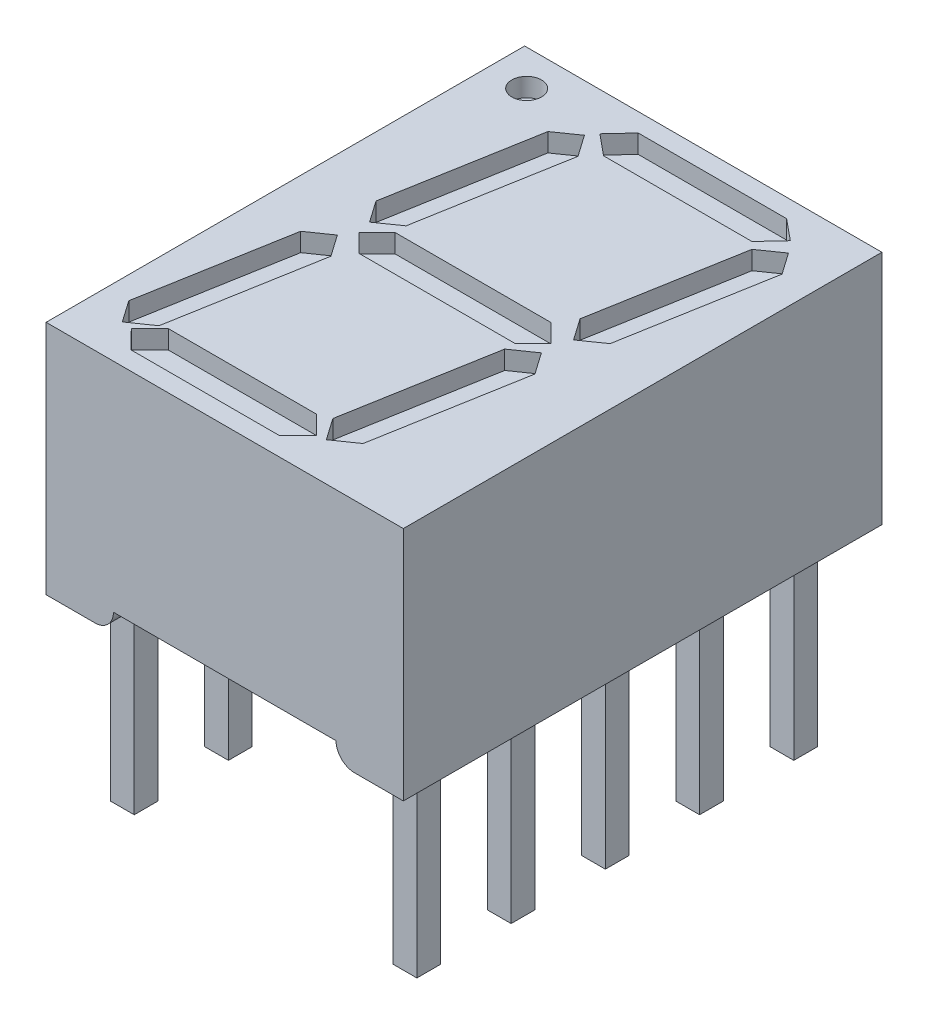
SolidWorks part; units mm, degrees
ref_plane "Front Plane" through (0, 0, 0) normal (0, 0, 1) x (1, 0, 0)
ref_plane "Top Plane" through (0, 0, 0) normal (0, 1, 0) x (1, 0, 0)
ref_plane "Right Plane" through (0, 0, 0) normal (1, 0, 0) x (0, 0, -1)
sketch "Sketch1" plane through (0, 0, 0) normal (0, 1, 0) x (1, 0, 0)
  line L1 (-4.815, -6.45) -> (4.815, -6.45)
  line L2 (-4.815, -6.45) -> (-4.815, 6.45)
  line L3 (-4.815, 6.45) -> (4.815, 6.45)
  line L4 (4.815, -6.45) -> (4.815, 6.45)
  line L5 (-4.815, -6.45) -> (4.815, 6.45) construction
  line L6 (-4.815, 6.45) -> (4.815, -6.45) construction
  point P0 (0, 0)
  dimension "D1" = 12.9
  dimension "D2" = 9.63
extrude "Boss-Extrude1" add sketch "Sketch1" along normal blind 6.36
sketch "Sketch2" plane through (0, 0, 0) normal (0, -1, 0) x (1, 0, 0)
  line L0 (-4.815, 6.45) -> (4.815, 6.45) construction
  line L1 (3, -6.45) -> (-3, -6.45)
  line L2 (3, -6.45) -> (3, 6.45)
  line L3 (3, 6.45) -> (-3, 6.45)
  line L4 (-3, -6.45) -> (-3, 6.45)
  line L5 (3, -6.45) -> (-3, 6.45) construction
  line L6 (3, 6.45) -> (-3, -6.45) construction
  line L7 (4.815, -6.45) -> (-4.815, -6.45) construction
  point P0 (0, 0)
  dimension "D1" = 6
extrude "Cut-Extrude1" cut sketch "Sketch2" against normal blind 0.5
fillet "Fillet1" radius 0.5 2 edges at (3, 0, 0) (-3, 0, 0)
sketch "Sketch3" plane through (0, 0, 0) normal (0, -1, 0) x (1, 0, 0)
  line L0 (-3.49, 2.86) -> (-4.13, 2.22) construction
  line L1 (3.81, -6.45) -> (-3.81, -6.45) construction
  line L2 (3.81, -6.45) -> (3.81, 6.45) construction
  line L3 (3.81, 6.45) -> (-3.81, 6.45) construction
  line L4 (-3.81, -6.45) -> (-3.81, 6.45) construction
  line L5 (3.81, -6.45) -> (-3.81, 6.45) construction
  line L6 (3.81, 6.45) -> (-3.81, -6.45) construction
  line L7 (3.5, 6.45) -> (4.815, 6.45) construction
  line L8 (4.815, -6.45) -> (3.5, -6.45) construction
  line L9 (-4.815, 0) -> (4.815, 0) construction
  line L10 (-4.815, -6.45) -> (-4.815, 6.45) construction
  line L11 (4.815, 6.45) -> (4.815, -6.45) construction
  line L12 (-4.815, 2.54) -> (4.815, 2.54) construction
  line L13 (-4.815, 5.08) -> (4.815, 5.08) construction
  line L14 (-4.815, -2.54) -> (4.815, -2.54) construction
  line L15 (-4.815, -5.08) -> (4.815, -5.08) construction
  line L16 (-3.49, 2.22) -> (-3.49, 2.86)
  line L17 (-3.49, 4.76) -> (-4.13, 4.76)
  line L18 (-3.49, 4.76) -> (-3.49, 5.4)
  line L19 (-3.49, 5.4) -> (-4.13, 5.4)
  line L20 (-4.13, 4.76) -> (-4.13, 5.4)
  line L21 (-3.49, 4.76) -> (-4.13, 5.4) construction
  line L22 (-3.49, 5.4) -> (-4.13, 4.76) construction
  line L23 (-3.49, 2.22) -> (-4.13, 2.22)
  line L24 (-4.13, 2.22) -> (-4.13, 2.86)
  line L25 (-3.49, 2.86) -> (-4.13, 2.86)
  line L26 (-3.49, 0.32) -> (-4.13, -0.32) construction
  line L27 (-3.49, -0.32) -> (-3.49, 0.32)
  line L28 (-3.49, -0.32) -> (-4.13, -0.32)
  line L29 (-4.13, -0.32) -> (-4.13, 0.32)
  line L30 (-3.49, 0.32) -> (-4.13, 0.32)
  line L31 (-3.49, -2.22) -> (-4.13, -2.86) construction
  line L32 (-3.49, -2.86) -> (-3.49, -2.22)
  line L33 (-3.49, -2.86) -> (-4.13, -2.86)
  line L34 (-4.13, -2.86) -> (-4.13, -2.22)
  line L35 (-3.49, -2.22) -> (-4.13, -2.22)
  line L36 (-3.49, -4.76) -> (-4.13, -5.4) construction
  line L37 (-3.49, -5.4) -> (-3.49, -4.76)
  line L38 (-3.49, -5.4) -> (-4.13, -5.4)
  line L39 (-4.13, -5.4) -> (-4.13, -4.76)
  line L40 (-3.49, -4.76) -> (-4.13, -4.76)
  line L45 (3.49, 2.22) -> (3.49, 2.86)
  line L46 (3.49, 4.76) -> (4.13, 4.76)
  line L47 (3.49, 4.76) -> (3.49, 5.4)
  line L48 (3.49, 5.4) -> (4.13, 5.4)
  line L49 (4.13, 4.76) -> (4.13, 5.4)
  line L50 (3.49, 4.76) -> (4.13, 5.4) construction
  line L51 (3.49, 5.4) -> (4.13, 4.76) construction
  line L52 (3.49, 2.22) -> (4.13, 2.22)
  line L53 (4.13, 2.22) -> (4.13, 2.86)
  line L54 (3.49, 2.86) -> (4.13, 2.86)
  line L55 (3.49, -0.32) -> (3.49, 0.32)
  line L56 (3.49, -0.32) -> (4.13, -0.32)
  line L57 (4.13, -0.32) -> (4.13, 0.32)
  line L58 (3.49, 0.32) -> (4.13, 0.32)
  line L59 (3.49, -2.86) -> (3.49, -2.22)
  line L60 (3.49, -2.86) -> (4.13, -2.86)
  line L61 (4.13, -2.86) -> (4.13, -2.22)
  line L62 (3.49, -2.22) -> (4.13, -2.22)
  line L63 (3.49, -5.4) -> (3.49, -4.76)
  line L64 (3.49, -5.4) -> (4.13, -5.4)
  line L65 (4.13, -5.4) -> (4.13, -4.76)
  line L66 (3.49, -4.76) -> (4.13, -4.76)
  point P0 (0, 0)
  point P24 (-3.81, 5.08)
  point P25 (-3.81, 2.54)
  point P26 (-3.81, 0)
  point P27 (-3.81, -2.54)
  point P28 (-3.81, -5.08)
  point P29 (3.81, -5.08)
  point P30 (3.81, -2.54)
  point P31 (3.81, 0)
  point P32 (3.81, 2.54)
  point P33 (3.81, 5.08)
  point P34 (-3.81, 5.08)
  point P40 (3.81, 5.08)
  dimension "D1" = 7.62
  dimension "D2" = 2.54
  dimension "D3" = 2.54
  dimension "D4" = 2.54
  dimension "D5" = 2.54
  dimension "D6" = 0.64
  dimension "D7" = 5
  dimension "D8" = 0.64
  dimension "D9" = 5
extrude "Boss-Extrude2" add sketch "Sketch3" along normal blind 5
sketch "Sketch4" plane through (0, 6.36, 0) normal (0, 1, 0) x (1, 0, 0)
  line L0 (4.815, 6.45) -> (2.5404, -6.45) construction
  line L1 (4.815, 6.45) -> (-4.815, 6.45) construction
  line L2 (-4.815, -6.45) -> (4.815, -6.45) construction
  line L3 (4.815, 6.45) -> (4.815, -6.45) construction
  line L4 (4.815, -6.45) -> (4.815, 6.45) construction
  line L5 (3.9798, 4.5928) -> (3.2852, 0.6536)
  line L6 (3.2852, 0.6536) -> (2.706, 0.248)
  line L7 (2.706, 0.248) -> (2.3004, 0.8273)
  line L8 (2.3004, 0.8273) -> (2.995, 4.7665)
  line L9 (2.995, 4.7665) -> (3.5742, 5.1721)
  line L10 (3.5742, 5.1721) -> (3.9798, 4.5928)
  line L11 (3.5742, 5.1721) -> (2.706, 0.248) construction
  line L12 (3.9798, 4.5928) -> (2.995, 4.7665) construction
  line L13 (3.2852, 0.6536) -> (2.3004, 0.8273) construction
  line L14 (2.9813, -1.0698) -> (2.2868, -5.009)
  line L15 (2.2868, -5.009) -> (1.7036, -5.4139)
  line L16 (1.7036, -5.4139) -> (1.2964, -4.8324)
  line L17 (1.2964, -4.8324) -> (1.9909, -0.8931)
  line L18 (1.9909, -0.8931) -> (2.5741, -0.4882)
  line L19 (2.5741, -0.4882) -> (2.9813, -1.0698)
  line L20 (-3.0216, -4.95) -> (0.9784, -4.95)
  line L21 (0.9784, -4.95) -> (1.4764, -5.45)
  line L22 (1.4764, -5.45) -> (0.9784, -5.95)
  line L23 (0.9784, -5.95) -> (-3.0216, -5.95)
  line L24 (-3.0216, -5.95) -> (-3.5195, -5.45)
  line L25 (-3.5195, -5.45) -> (-3.0216, -4.95)
  line L26 (0.9784, -4.95) -> (0.9784, -5.95) construction
  line L27 (-3.0216, -4.95) -> (-3.0216, -5.95) construction
  line L28 (1.4764, -5.45) -> (-3.5195, -5.45) construction
  line L29 (-2.208, 0.3501) -> (1.992, 0.3501)
  line L36 (-1.2541, 5.95) -> (2.7459, 5.95)
  line L37 (2.7459, 5.95) -> (3.3111, 5.4858)
  line L38 (3.3111, 5.4858) -> (2.8131, 4.95)
  line L39 (2.8131, 4.95) -> (-1.1869, 4.95)
  line L40 (-1.1869, 4.95) -> (-1.7521, 5.4142)
  line L41 (-1.7521, 5.4142) -> (-1.2541, 5.95)
  line L42 (-2.5187, -1.0698) -> (-3.2132, -5.009)
  line L43 (-3.2132, -5.009) -> (-3.7964, -5.4139)
  line L44 (-3.7964, -5.4139) -> (-4.2036, -4.8324)
  line L45 (-4.2036, -4.8324) -> (-3.5091, -0.8931)
  line L46 (-3.5091, -0.8931) -> (-2.9259, -0.4882)
  line L47 (-2.9259, -0.4882) -> (-2.5187, -1.0698)
  line L48 (-1.9258, 5.1721) -> (-1.5202, 4.5928)
  line L49 (-1.5202, 4.5928) -> (-2.2148, 0.6536)
  line L50 (-2.2148, 0.6536) -> (-2.794, 0.248)
  line L51 (-2.794, 0.248) -> (-3.1996, 0.8273)
  line L52 (-3.1996, 0.8273) -> (-2.505, 4.7665)
  line L53 (-2.505, 4.7665) -> (-1.9258, 5.1721)
  line L54 (1.992, 0.3501) -> (2.4771, -0.137)
  line L55 (2.4771, -0.137) -> (1.992, -0.6241)
  line L56 (1.992, -0.6241) -> (-2.208, -0.6241)
  line L57 (-2.208, -0.6241) -> (-2.6931, -0.137)
  line L58 (-2.6931, -0.137) -> (-2.208, 0.3501)
  circle A0 centre (-3.7964, 5.4858) radius 0.4
  dimension "D17" = 0.8
  dimension "D1" = 2.2746
  dimension "D2" = 4
  dimension "D3" = 1
  dimension "D4" = 0.5
  dimension "D5" = 0.5
  dimension "D6" = 0.5
  dimension "D7" = 0.5
  dimension "D8" = 1
  dimension "D9" = 1.75
  dimension "D10" = 1
  dimension "D11" = 4
  dimension "D12" = 0.5
  dimension "D13" = 0.5
  dimension "D14" = 1
  dimension "D15" = 4
  dimension "D18" = 4.2
  dimension "D16" = 2
extrude "Cut-Extrude2" cut sketch "Sketch4" against normal blind 0.5
